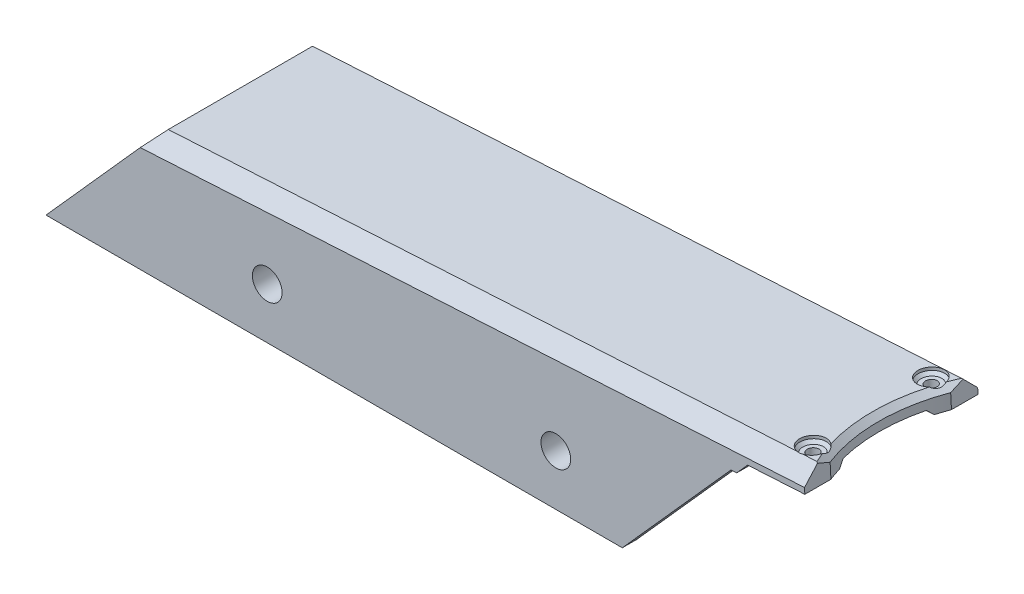
SolidWorks part; units mm, degrees
ref_plane "Plan de face" through (0, 0, 0) normal (0, 0, 1) x (1, 0, 0)
ref_plane "Plan de dessus" through (0, 0, 0) normal (0, 1, 0) x (1, 0, 0)
ref_plane "Plan de droite" through (0, 0, 0) normal (1, 0, 0) x (0, 0, -1)
sketch "Esquisse1" plane through (0, 0, 0) normal (0, 0, 1) x (1, 0, 0)
  line L0 (-49.925, 0) -> (49.925, 0)
  line L1 (-49.925, 0) -> (-36.5626, 14.9723)
  line L2 (49.925, 0) -> (68.6211, 20.9486)
  line L3 (68.6211, 20.9486) -> (-36.5626, 14.9723)
  line L6 (49.925, 0) -> (64.2174, 16.0144) construction
  line L7 (-50.075, 0) -> (-41.1244, 10.029) construction
  line L8 (-26.5878, 15.539) -> (58.4883, 20.3729) construction
  circle A0 centre (-11.5923, 8.8036) radius 2.575
  circle A1 centre (38.4077, 8.8036) radius 2.575
  circle A2 centre (38.4077, 8.8036) radius 2.575 construction
  point P4 (0, 0)
  dimension "D1" = 99.85
  dimension "D2" = 131.748
  dimension "D3" = 45
extrude "Boss.-Extru.1" add sketch "Esquisse1" against normal blind 5
sketch "Esquisse2" plane through (0, 0, 0) normal (0, 0, 1) x (1, 0, 0)
  line L0 (-36.5626, 14.9723) -> (68.6211, 20.9486)
  line L1 (68.6211, 20.9486) -> (-36.5626, 14.9723) construction
  line L2 (68.6211, 20.9486) -> (73.9415, 26.91)
  line L3 (73.9415, 26.91) -> (-31.2422, 20.9337)
  line L4 (-31.2422, 20.9337) -> (-36.5626, 14.9723)
  line L5 (-36.5626, 14.9723) -> (-49.925, 0) construction
  line L6 (49.925, 0) -> (68.6211, 20.9486) construction
  line L11 (73.9415, 26.91) -> (81.3542, 27.3312)
  line L12 (81.3542, 27.3312) -> (81.496, 24.8353)
  line L13 (81.496, 24.8353) -> (71.5873, 24.2723)
  line L17 (79.799, 27.6936) -> (79.9833, 24.4488) construction
  line L21 (73.6622, 24.2399) -> (81.153, 24.6655) construction
  line L22 (71.5873, 24.2723) -> (73.9415, 26.91)
  dimension "D1" = 2.5
  dimension "D2" = 0.15
  dimension "D3" = 0.15
extrude "Boss.-Extru.2" add sketch "Esquisse2" against normal blind 5 contours L3 L4 L0 L2 | L13 L12 L11 L2 region at (18.6894, 20.9412, 0) region at (77.0682, 25.7756, 0)
sketch "Esquisse3" plane through (0, 0, -5) normal (0, 0, -1) x (-1, 0, 0)
  line L0 (-81.3542, 27.3312) -> (31.2422, 20.9337)
  line L1 (-81.3542, 27.3312) -> (31.2422, 20.9337) construction
  line L2 (-81.3542, 27.3312) -> (-81.496, 24.8353)
  line L3 (-81.496, 24.8353) -> (33.5964, 18.2959)
  line L4 (33.5964, 18.2959) -> (31.2422, 20.9337)
  line L5 (-81.3542, 27.3312) -> (-81.496, 24.8353) construction
  line L9 (31.2422, 20.9337) -> (49.925, 0) construction
extrude "Boss.-Extru.3" add sketch "Esquisse3" along normal up to surface (25 mm away)
sketch "Esquisse4" plane through (-1.1443, 20.1398, 0) normal (0.0567, -0.9984, 0) x (0.9984, 0.0567, 0)
  line L0 (82.7736, 0) -> (72.8489, 0)
  line L1 (72.8489, 0) -> (72.8489, -7.8)
  line L2 (72.8489, -7.8) -> (82.7736, -7.8)
  line L3 (82.7736, -7.8) -> (82.7736, 0)
  line L4 (82.7736, -30) -> (82.7736, 0) construction
  line L5 (82.7736, 0) -> (72.8489, 0) construction
  line L6 (72.8489, -5) -> (72.8489, 0) construction
  line L7 (72.8489, -22.2) -> (82.7736, -22.2)
  line L12 (99.7848, -15) -> (65.7624, -15) construction
  line L13 (72.8489, -30) -> (72.8489, -22.2)
  line L14 (82.7736, -30) -> (72.8489, -30)
  line L15 (82.7736, -22.2) -> (82.7736, -30)
  point P20 (82.7736, -15)
  dimension "D1" = 7.8
extrude "Boss.-Extru.4" add sketch "Esquisse4" along normal blind 1
sketch "Esquisse5" plane through (-1.1443, 20.1398, 0) normal (0.0567, -0.9984, 0) x (0.9984, 0.0567, 0)
  circle A0 centre (79.5914, -25.2117) radius 1
  circle A1 centre (79.5914, -4.7117) radius 1
  dimension "D1" = 2
extrude "Enlèv. mat.-Extru.1" cut sketch "Esquisse5" against normal through all both and the other way through all contours A1 | A0
sketch "Esquisse6" plane through (-1.1443, 20.1398, 0) normal (0.0567, -0.9984, 0) x (0.9984, 0.0567, 0)
  line L0 (82.7736, -4.5184) -> (82.7736, -25.405)
  line L4 (82.7736, -30) -> (82.7736, 0) construction
  arc A0 (82.7736, -25.405) -> (82.7736, -4.5184) centre (108.5914, -14.9617) cw
  point P11 (82.7736, -14.9617)
  dimension "D1" = 27.85
extrude "Enlèv. mat.-Extru.2" cut sketch "Esquisse6" against normal through all and the other way through all
sketch "Esquisse7" plane through (-1.1443, 20.1398, 0) normal (0.0567, -0.9984, 0) x (0.9984, 0.0567, 0)
  line L0 (72.8489, 0) -> (72.8489, -30)
  line L1 (72.8489, -30) -> (-32.5044, -30)
  line L2 (-32.5044, -30) -> (-32.5044, 0)
  line L3 (-32.5044, 0) -> (72.8489, 0)
  line L4 (-32.5044, -30) -> (72.8489, -30) construction
  line L6 (82.7736, 0) -> (-30.0044, 0) construction
  line L7 (-32.5044, -30) -> (-32.5044, -5) construction
  line L8 (72.8489, 0) -> (72.8489, -7.8) construction
extrude "Boss.-Extru.5" add sketch "Esquisse7" along normal blind 3
chamfer "Chanfrein1" distance 2.5 angle 45 1 edges at (-41.7607, 9.148, -5)
chamfer "Chanfrein2" distance 2.5 angle 45 1 edges at (59.3437, 10.5535, -5)
chamfer "Chanfrein3" distance 2.7 angle 60 1 edges at (16.1705, 18.1187, -5) first distance on face at (40.9827, 8.8036, -5)
chamfer "Chanfrein4" distance 2.5 angle 45 1 edges at (25.056, 24.1325, 0)
chamfer "Chanfrein5" distance 2.5 angle 45 1 edges at (25.056, 24.1325, -30)
sketch "Esquisse9" plane through (-1.2861, 22.6358, 0) normal (-0.0567, 0.9984, 0) x (0.9984, 0.0567, 0)
  circle A0 centre (79.5914, 25.2117) radius 2.25
  circle A1 centre (79.5914, 4.7117) radius 2.25
  dimension "D1" = 4.5
extrude "Enlèv. mat.-Extru.3" cut sketch "Esquisse9" against normal blind 1
chamfer "Chanfrein6" distance 0.5 angle 45 2 edges at (75.9875, 26.0247, -4.7117) (75.9875, 26.0247, -25.2117)
chamfer "Chanfrein7" distance 1 angle 45 1 edges at (79.3253, 27.2159, -14.9617)
chamfer "Chanfrein8" distance 2 angle 45 2 edges at (71.7575, 21.2771, -15) (19.1657, 18.2889, -30)
chamfer "Chanfrein9" distance 1 angle 45 1 edges at (76.0515, 23.5243, -7.8)
chamfer "Chanfrein10" distance 1 angle 45 1 edges at (76.0617, 23.5249, -22.2)
equation "\"3.50mm-\"=3.5"
